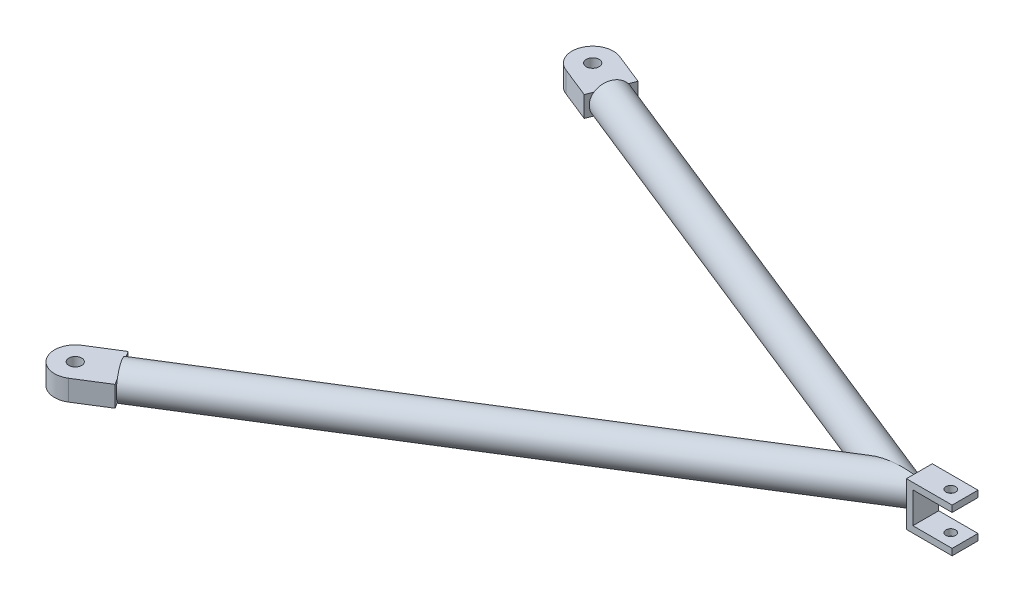
SolidWorks part; units mm, degrees
ref_plane "Front Plane" through (0, 0, 0) normal (0, 0, 1) x (1, 0, 0)
ref_plane "Top Plane" through (0, 0, 0) normal (0, 1, 0) x (1, 0, 0)
ref_plane "Right Plane" through (0, 0, 0) normal (1, 0, 0) x (0, 0, -1)
sketch "Sketch1" plane through (0, 0, 0) normal (0, 1, 0) x (1, 0, 0)
  line L0 (0, 0) -> (-247.6207, 99.06)
  line L1 (0, 0) -> (-247.6207, -154.94)
  line L2 (-247.6207, 99.06) -> (-247.6207, -154.94) construction
  dimension "D1" = 266.7
  dimension "D2" = 292.1
  dimension "D3" = 254
ref_plane "Plane1" through (-247.6207, 0, 154.94) normal (-0.8477, 0, 0.5304) x (0.5304, 0, 0.8477)
sketch "Sketch2" plane through (-247.6207, 0, 154.94) normal (-0.8477, 0, 0.5304) x (0.5304, 0, 0.8477)
  circle A0 centre (0, 0) radius 8.255
  dimension "D1" = 16.51
sweep "Sweep1" add profiles "Sketch2" path "Sketch1"
sketch "Sketch3" plane through (0, 0, 0) normal (0, 0, 1) x (1, 0, 0)
  line L0 (34.2567, -10.795) -> (11.811, -10.795)
  line L1 (11.811, -10.795) -> (11.811, 10.795)
  line L2 (11.811, 10.795) -> (34.2567, 10.795)
  line L3 (34.2567, 10.795) -> (34.2567, 7.62)
  line L4 (34.2567, 7.62) -> (14.986, 7.62)
  line L5 (14.986, 7.62) -> (14.986, -7.62)
  line L6 (14.986, -7.62) -> (34.2567, -7.62)
  line L7 (34.2567, -7.62) -> (34.2567, -10.795)
  line L8 (-18.161, 0) -> (18.161, 0) construction
  ellipse E0 centre (0, 0) end of major axis (18.161, 0) minor radius 8.255 construction
  ellipse E1 centre (0, 0) end of major axis (18.161, 0) minor radius 8.255 construction
  point P21 (11.811, 0)
  dimension "D1" = 3.175
  dimension "D2" = 15.24
  dimension "D3" = 3.175
  dimension "D4" = 6.35
extrude "Boss-Extrude1" add sketch "Sketch3" along normal blind 6.35 and the other way blind 6.35
sketch "Sketch4" plane through (-247.6207, 0, 154.94) normal (-0.8477, 0, 0.5304) x (0.5304, 0, 0.8477)
  line L1 (-10.16, 5.08) -> (10.16, 5.08)
  line L2 (-10.16, 5.08) -> (-10.16, -5.08)
  line L3 (-10.16, -5.08) -> (10.16, -5.08)
  line L4 (10.16, 5.08) -> (10.16, -5.08)
  line L5 (-10.16, 5.08) -> (10.16, -5.08) construction
  line L6 (-10.16, -5.08) -> (10.16, 5.08) construction
  point P0 (0, 0)
  dimension "D1" = 20.32
  dimension "D2" = 10.16
extrude "Boss-Extrude2" add sketch "Sketch4" along normal blind 10.16 and the other way blind 16.51
sketch "Sketch5" plane through (-247.6207, 0, -99.06) normal (-0.9285, 0, -0.3714) x (-0.3714, 0, 0.9285)
  line L1 (-10.16, 5.08) -> (10.16, 5.08)
  line L2 (-10.16, 5.08) -> (-10.16, -5.08)
  line L3 (-10.16, -5.08) -> (10.16, -5.08)
  line L4 (10.16, 5.08) -> (10.16, -5.08)
  line L5 (-10.16, 5.08) -> (10.16, -5.08) construction
  line L6 (-10.16, -5.08) -> (10.16, 5.08) construction
  point P0 (0, 0)
  dimension "D1" = 20.32
  dimension "D2" = 10.16
extrude "Boss-Extrude3" add sketch "Sketch5" along normal blind 10.16 and the other way blind 16.256
sketch "Sketch7" plane through (0, 5.08, 0) normal (0, 1, 0) x (1, 0, 0)
  line L8 (-236.3013, 83.5889) -> (-234.9444, 86.9807)
  line L9 (-234.9444, 86.9807) -> (-250.0375, 93.0187)
  line L10 (-250.0375, 93.0187) -> (-245.2039, 105.1013)
  line L11 (-245.2039, 105.1013) -> (-230.1108, 99.0634)
  line L12 (-230.1108, 99.0634) -> (-228.7539, 102.4552)
  line L13 (-228.7539, 102.4552) -> (-253.2801, 112.2669)
  line L14 (-253.2801, 112.2669) -> (-260.8276, 93.4005)
  line L15 (-260.8276, 93.4005) -> (-236.3013, 83.5889)
  line L22 (-257.0539, 102.8337) -> (-260.8276, 93.4005)
  line L23 (-260.8276, 93.4005) -> (-251.3944, 89.6268)
  arc A0 (-257.0539, 102.8337) -> (-251.3944, 89.6268) centre (-247.6207, 99.06) ccw
  dimension "D1" = 0
extrude "Cut-Extrude1" cut sketch "Sketch7" against normal through all
ref_plane "Plane2" through (0, 0, 0) normal (-0.3714, 0, 0.9285) x (0.9285, 0, 0.3714)
mirror "Mirror1" about plane through (0, 0, 0) normal (-0.3714, 0, 0.9285) of "Cut-Extrude1"
sketch "Sketch9" plane through (0, 5.08, 0) normal (0, 1, 0) x (1, 0, 0)
  line L0 (-239.014, -137.5696) -> (-261.6228, -151.7163) construction
  line L1 (-228.2355, -154.7954) -> (-250.8444, -168.9421) construction
  line L2 (-250.8444, -168.9421) -> (-261.6228, -151.7163) construction
  line L3 (-242.2315, -163.5529) -> (-250.8444, -168.9421)
  line L4 (-250.8444, -168.9421) -> (-256.2336, -160.3292)
  arc A0 (-256.2336, -160.3292) -> (-242.2315, -163.5529) centre (-247.6207, -154.94) ccw
extrude "Cut-Extrude2" cut sketch "Sketch9" against normal through all
ref_plane "Plane3" through (0, 0, 0) normal (0.5304, 0, 0.8477) x (0.8477, 0, -0.5304)
mirror "Mirror2" about plane through (0, 0, 0) normal (0.5304, 0, 0.8477) of "Cut-Extrude2"
sketch "Sketch10" plane through (-247.6207, 0, 154.94) normal (-0.8477, 0, 0.5304) x (0.5304, 0, 0.8477)
  line L0 (6.5068, -5.08) -> (-6.5068, -5.08) construction
  line L1 (-6.5068, 5.08) -> (6.5068, 5.08) construction
  line L2 (6.5068, -5.08) -> (-6.5068, -5.08)
  line L3 (-6.5068, 5.08) -> (6.5068, 5.08)
  arc A0 (-6.5068, -5.08) -> (6.5068, -5.08) centre (0, 0) ccw construction
  arc A1 (6.5068, 5.08) -> (-6.5068, 5.08) centre (0, 0) ccw construction
  arc A2 (-6.5068, -5.08) -> (6.5068, -5.08) centre (0, 0) ccw
  arc A3 (6.5068, 5.08) -> (-6.5068, 5.08) centre (0, 0) ccw
extrude "Cut-Extrude3" cut sketch "Sketch10" against normal up to surface (16.51 mm away) up to face at (-228.9726, 0, 153.6175)
sketch "Sketch11" plane through (-247.6207, 0, -99.06) normal (-0.9285, 0, -0.3714) x (-0.3714, 0, 0.9285)
  line L0 (6.5068, -5.08) -> (-6.5068, -5.08) construction
  line L1 (-6.5068, 5.08) -> (6.5068, 5.08) construction
  line L2 (6.5068, -5.08) -> (-6.5068, -5.08)
  line L3 (-6.5068, 5.08) -> (6.5068, 5.08)
  arc A0 (-6.5068, -5.08) -> (6.5068, -5.08) centre (0, 0) ccw construction
  arc A1 (6.5068, 5.08) -> (-6.5068, 5.08) centre (0, 0) ccw construction
  arc A2 (-6.5068, -5.08) -> (6.5068, -5.08) centre (0, 0) ccw
  arc A3 (6.5068, 5.08) -> (-6.5068, 5.08) centre (0, 0) ccw
extrude "Cut-Extrude4" cut sketch "Sketch11" along direction (0.9285, 0, 0.3714) on the side against the normal up to surface (16.256 mm away) up to face at (-235.7852, 0, -84.879)
sketch "Sketch12" plane through (0, 0, 6.35) normal (0, 0, 1) x (1, 0, 0)
  line L1 (14.986, 4.6631) -> (14.986, -4.6631)
  line L2 (14.986, 4.6631) -> (14.986, -4.6631)
  ellipse E1 centre (0, 0) end of major axis (18.161, 0) minor radius 8.255 (14.986, -4.6631) -> (14.986, 4.6631) ccw
  ellipse E2 centre (0, 0) end of major axis (18.161, 0) minor radius 8.255 (14.986, -4.6631) -> (14.986, 4.6631) ccw
  dimension "D1" = 0
extrude "Cut-Extrude5" cut sketch "Sketch12" against normal through all
sketch "Sketch13" plane through (0, 5.08, 0) normal (0, 1, 0) x (1, 0, 0)
  point P0 (-247.6207, 99.06)
  point P1 (-247.6207, -154.94)
hole_wizard "E (0.25) Diameter Hole1" positions "3DSketch1" profile "Sketch14" hole size "E" standard "ANSI Inch"
sketch3d "3DSketch1"
  point P0 (-247.6207, 5.08, -99.06)
  point P3 (-247.6207, 5.08, 154.94)
sketch "Sketch14" plane through (-247.6207, 5.08, -99.06) normal (1, 0, 0) x (0, 0, 1)
  line L0 (0, 0) -> (0, 20.9577)
  line L1 (0, 20.9577) -> (3.175, 19.05)
  line L2 (3.175, 19.05) -> (3.175, 0)
  line L5 (3.175, 0) -> (0, 0)
  line L10 (0, 20.9577) -> (-3.175, 19.05) construction
  line L11 (0, -6.35) -> (0, 107.95) construction
  dimension "Hole Dia." = 6.35
  dimension "Hole Depth" = 19.05
  dimension "Drill Angle" = 118
hole_wizard "3/16 (0.1875) Diameter Hole1" positions "Sketch15" profile "Sketch16" hole size "3/16" standard "ANSI Inch" end condition through all
sketch "Sketch15" plane through (0, 10.795, 0) normal (0, 1, 0) x (1, 0, 0)
  line L0 (-11.8745, 0) -> (11.8745, 0) construction
  point P0 (27.2415, 0)
sketch "Sketch16" plane through (27.2415, 10.795, 0) normal (1, 0, 0) x (0, 0, 1)
  line L0 (0, 0) -> (0, 21.59)
  line L1 (0, 21.59) -> (2.3812, 21.59)
  line L2 (2.3812, 21.59) -> (2.3812, 0)
  line L5 (2.3812, 0) -> (0, 0)
  line L11 (0, -6.35) -> (0, 107.95) construction
  dimension "Thru Hole Dia." = 4.7625
  dimension "Thru Hole Depth" = 21.59
